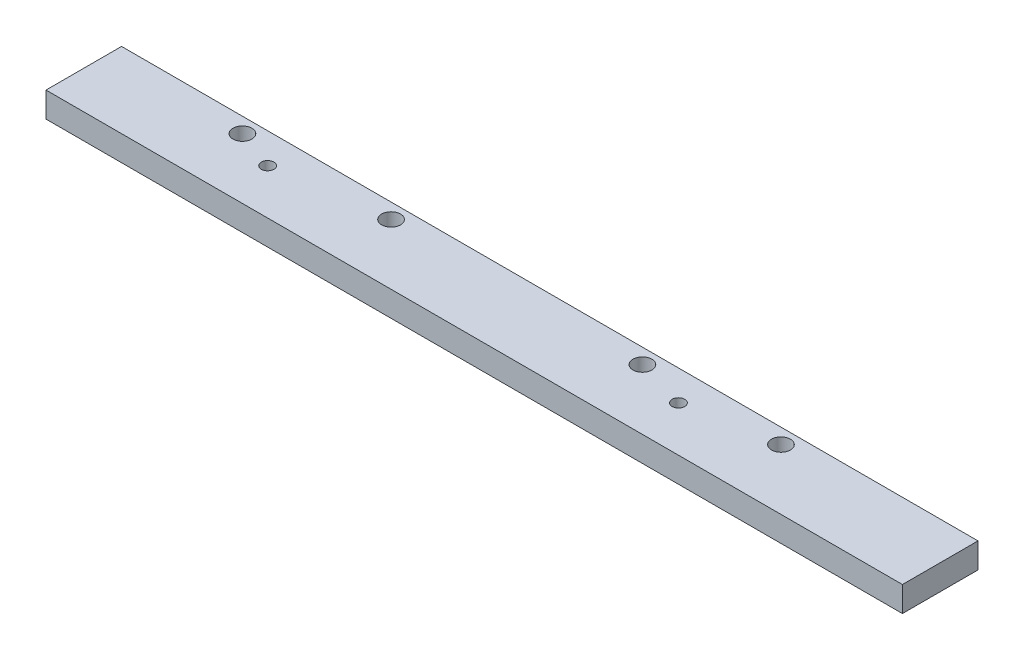
SolidWorks part; units mm, degrees
ref_plane "Front Plane" through (0, 0, 0) normal (0, 0, 1) x (1, 0, 0)
ref_plane "Top Plane" through (0, 0, 0) normal (0, 1, 0) x (1, 0, 0)
ref_plane "Right Plane" through (0, 0, 0) normal (1, 0, 0) x (0, 0, -1)
sketch "Sketch1" plane through (0, 0, 0) normal (0, 1, 0) x (1, 0, 0)
  line L1 (0, 0) -> (431.8, 0)
  line L2 (0, 0) -> (0, 38.1)
  line L3 (0, 38.1) -> (431.8, 38.1)
  line L4 (431.8, 0) -> (431.8, 38.1)
  circle A0 centre (68.5591, 30.48) radius 4.7625
  circle A1 centre (143.4891, 30.48) radius 4.7625
  circle A2 centre (270.2275, 30.48) radius 4.7625
  circle A3 centre (340.0775, 30.48) radius 4.7625
  circle A4 centre (88.9, 22.8376) radius 3.175
  circle A5 centre (296.037, 22.8376) radius 3.175
  point P15 (46.3296, 25.146)
  point P18 (0, 0)
  point P19 (475.3911, 22.8376)
  point P20 (68.5591, 25.146)
  dimension "D3" = 9.525
  dimension "D5" = 9.525
  dimension "D6" = 126.7384
  dimension "D7" = 69.85
  dimension "D8" = 9.525
  dimension "D9" = 9.525
  dimension "D11" = 6.35
  dimension "D12" = 6.35
  dimension "D1" = 38.1
  dimension "D2" = 431.8
  dimension "D4" = 74.93
  dimension "D10" = 207.137
  dimension "D13" = 15.2624
  dimension "D14" = 7.62
  dimension "D15" = 88.9
extrude "Boss-Extrude1" add sketch "Sketch1" along normal blind 12.7
sketch "Sketch2" plane through (0, 12.7, 0) normal (0, 1, 0) x (1, 0, 0)
  line L0 (231.7774, 29.7419) -> (231.7774, 12.5045)
  line L1 (438.9144, 28.4445) -> (438.9144, 12.5045)
  dimension "D1" = 207.137
